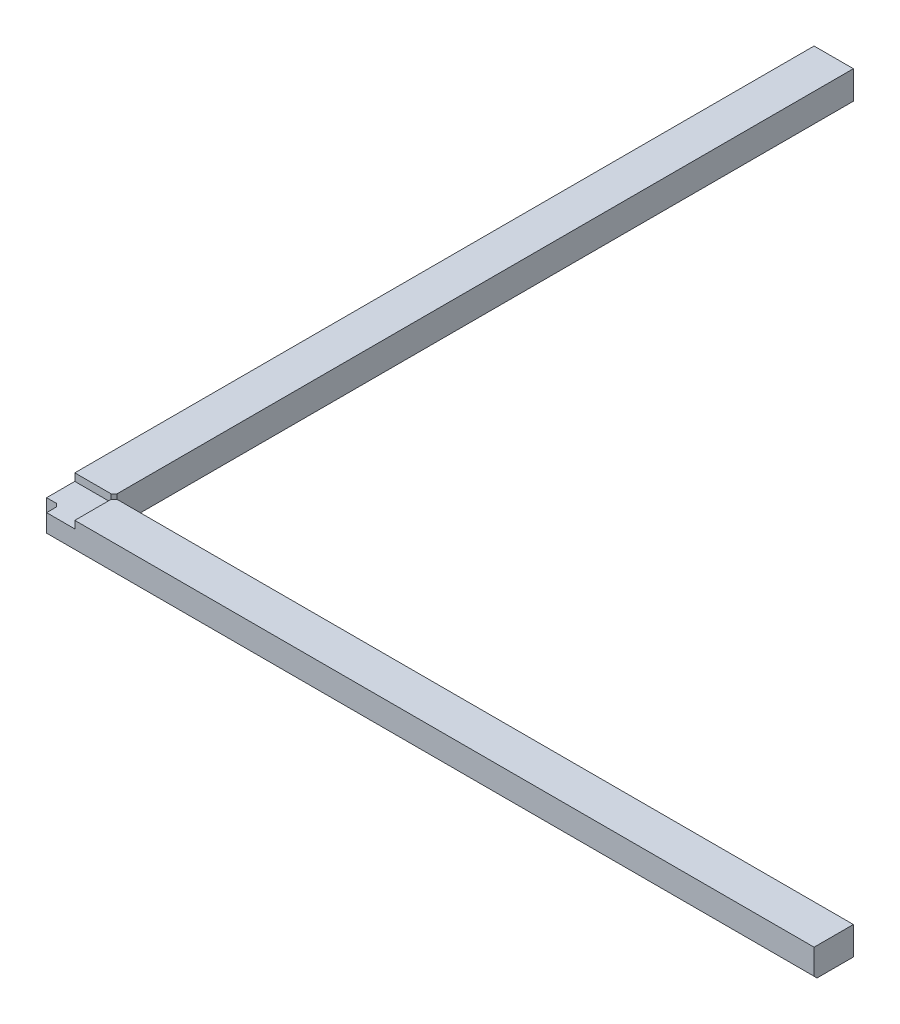
SolidWorks part; units mm, degrees
ref_plane "Plan de face" through (0, 0, 0) normal (0, 0, 1) x (1, 0, 0)
ref_plane "Plan de dessus" through (0, 0, 0) normal (0, 1, 0) x (1, 0, 0)
ref_plane "Plan de droite" through (0, 0, 0) normal (1, 0, 0) x (0, 0, -1)
sketch "Esquisse1" plane through (0, 0, 0) normal (0, 1, 0) x (1, 0, 0)
  line L0 (0, 0) -> (105.25, 0)
  line L1 (105.25, 0) -> (105.25, 5.3)
  line L2 (105.25, 5.3) -> (5.3, 5.3)
  line L3 (5.3, 5.3) -> (5.3, 105.25)
  line L4 (5.3, 105.25) -> (0, 105.25)
  line L5 (0, 105.25) -> (0, 0)
  dimension "D1" = 105.25
  dimension "D2" = 5.3
extrude "Boss.-Extru.1" add sketch "Esquisse1" along normal blind 3.8
sketch "Esquisse2" plane through (0, 3.8, 0) normal (0, 1, 0) x (1, 0, 0)
  line L0 (5.3, 5.55) -> (0, 5.55)
  line L1 (5.3, 5.3) -> (5.3, 105.25) construction
  line L2 (0, 105.25) -> (0, 0) construction
  line L3 (0, 5.55) -> (0, 0)
  line L4 (0, 0) -> (5.55, 0)
  line L5 (0, 0) -> (105.25, 0) construction
  line L6 (5.55, 0) -> (5.55, 5.3)
  line L7 (105.25, 5.3) -> (5.3, 5.3) construction
  line L8 (5.55, 5.3) -> (5.3, 5.3)
  line L9 (5.3, 5.3) -> (5.3, 5.55)
  dimension "D1" = 5.55
extrude "Enlèv. mat.-Extru.1" cut sketch "Esquisse2" against normal blind 1
sketch "Esquisse3" plane through (0, 2.8, 0) normal (0, 1, 0) x (1, 0, 0)
  line L1 (0, 0) -> (1.75, 0)
  line L2 (0, 0) -> (0, 1.75)
  line L3 (0, 1.75) -> (1.75, 1.75)
  line L4 (1.75, 0) -> (1.75, 1.75)
  dimension "D1" = 1.75
extrude "Enlèv. mat.-Extru.2" cut sketch "Esquisse3" against normal up to next
chamfer "Chanfrein1" distance 0.4 angle 45 5 edges at (1.75, 1.4, -1.75) (5.55, 3.3, -5.3) (5.3, 3.3, -5.55) (53.5, 0, 0) (0, 0, -53.5)
